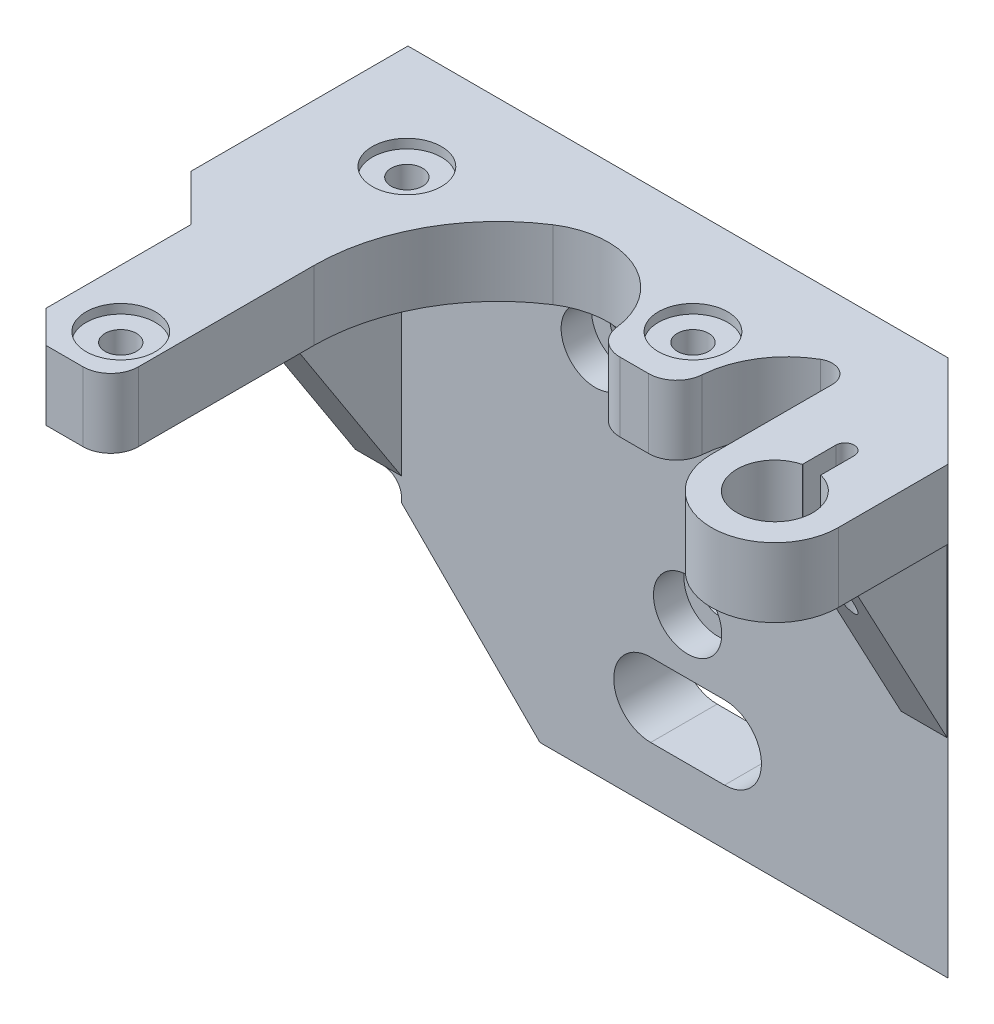
SolidWorks part; units mm, degrees
material "ABS"
ref_plane "Płaszczyzna przednia" through (0, 0, 0) normal (0, 0, 1) x (1, 0, 0)
ref_plane "Płaszczyzna górna" through (0, 0, 0) normal (0, 1, 0) x (1, 0, 0)
ref_plane "Płaszczyzna prawa" through (0, 0, 0) normal (1, 0, 0) x (0, 0, -1)
sketch "Szkic1" plane through (0, 0, 0) normal (0, 0, 1) x (1, 0, 0)
  line L0 (0, -10) -> (0, 10) construction
  line L1 (-10, 10) -> (10, 10) construction
  line L3 (-34, 22.5) -> (31, 22.5)
  line L4 (-34, 22.5) -> (-34, -30)
  line L5 (-34, -30) -> (31, -30)
  line L6 (31, 22.5) -> (31, -30)
  circle A0 centre (10, 10) radius 1.7
  circle A1 centre (-10, 10) radius 1.7
  circle A2 centre (0, -10) radius 1.7
  point P4 (0, 0)
  point P8 (0, 10)
  dimension "D1" = 3.4
  dimension "D2" = 20
  dimension "D3" = 20
  dimension "D4" = 24
  dimension "D5" = 21
  dimension "D6" = 20
  dimension "D7" = 12.5
extrude "Dodanie-wyciągnięcie1" add sketch "Szkic1" along normal blind 7.2
sketch "Szkic2" plane through (0, 0, 0) normal (0, 0, -1) x (-1, 0, 0)
  line L1 (-31, -30) -> (-8.8, -30)
  line L2 (-31, -30) -> (-31, -12.8)
  line L3 (-31, -12.8) -> (-8.8, -12.8)
  line L4 (-8.8, -30) -> (-8.8, -12.8)
  circle A0 centre (0, -10) radius 1.7 construction
  dimension "D1" = 8.8
  dimension "D2" = 2.8
extrude "Wytnij-wyciągnięcie1" cut sketch "Szkic2" against normal blind 3.4
fillet "Zaokrąglenie1" radius 2 1 edges at (8.8, -21.4, 3.4)
sketch "Szkic3" plane through (0, 0, 7.2) normal (0, 0, -1) x (-1, 0, 0)
  circle A0 centre (-10, 10) radius 3.7
  circle A1 centre (10, 10) radius 3.7
  circle A2 centre (0, -10) radius 3.7
  dimension "D1" = 7.4
extrude "Wytnij-wyciągnięcie2" cut sketch "Szkic3" along normal blind 3.3
sketch "Szkic4" plane through (0, 0, 7.2) normal (0, 0, 1) x (1, 0, 0)
  line L1 (31, 22.5) -> (20.5, 22.5)
  line L2 (31, 22.5) -> (31, 15)
  line L3 (31, 15) -> (20.5, 15)
  line L4 (20.5, 22.5) -> (20.5, 15)
  point P4 (10, 10)
  dimension "D1" = 10.5
  dimension "D2" = 5
extrude "Dodanie-wyciągnięcie2" add sketch "Szkic4" along normal blind 42
sketch "Szkic5" plane through (0, 22.5, 0) normal (0, 1, 0) x (1, 0, 0)
  line L0 (24.75, -43.865) -> (24.75, -12.865) construction
  line L1 (24.75, -12.865) -> (24.75, -7.2) construction
  line L2 (24.75, -7.2) -> (10, -7.2) construction
  line L3 (6.3, -7.2) -> (13.7, -7.2) construction
  circle A0 centre (24.75, -12.865) radius 3.75
  circle A1 centre (24.75, -43.865) radius 3.75
  dimension "D1" = 14.75
  dimension "D2" = 7.5
  dimension "D3" = 5.665
  dimension "D4" = 31
extrude "Wytnij-wyciągnięcie3" cut sketch "Szkic5" against normal blind 1
sketch "Szkic6" plane through (0, 21.5, 0) normal (0, 1, 0) x (1, 0, 0)
  circle A0 centre (24.75, -43.865) radius 1.7
  circle A1 centre (24.75, -12.865) radius 1.7
  dimension "D1" = 3.4
extrude "Wytnij-wyciągnięcie4" cut sketch "Szkic6" against normal up to next
fillet "Zaokrąglenie2" radius 20 1 edges at (20.5, 18.75, 7.2)
chamfer "Sfazowanie1" distance 3.5 angle 45 1 edges at (31, 18.75, 49.2)
sketch "Szkic7" plane through (0, 0, 7.2) normal (0, 0, 1) x (1, 0, 0)
  line L0 (0.5, 22.5) -> (-34, 22.5) construction
  line L1 (-1.75, 22.5) -> (-10.75, 22.5)
  line L2 (-1.75, 22.5) -> (-1.75, 15)
  line L3 (-1.75, 15) -> (-10.75, 15)
  line L4 (-10.75, 22.5) -> (-10.75, 15)
  line L5 (0.5, 15) -> (31, 15) construction
  line L6 (-34, 22.5) -> (-34, -30) construction
  dimension "D1" = 23.25
  dimension "D2" = 9
extrude "Dodanie-wyciągnięcie3" add sketch "Szkic7" along normal blind 12
sketch "Szkic8" plane through (0, 22.5, 0) normal (0, 1, 0) x (1, 0, 0)
  line L0 (24.75, -43.865) -> (24.75, -12.865) construction
  line L1 (24.75, -12.865) -> (-6.25, -12.865) construction
  circle A0 centre (-6.25, -12.865) radius 1.7
  circle A1 centre (24.75, -12.865) radius 1.7 construction
extrude "Wytnij-wyciągnięcie5" cut sketch "Szkic8" against normal up to next
sketch "Szkic9" plane through (0, 22.5, 0) normal (0, 1, 0) x (1, 0, 0)
  circle A0 centre (-6.25, -12.865) radius 3.75
  circle A1 centre (24.75, -12.865) radius 3.75 construction
extrude "Wytnij-wyciągnięcie6" cut sketch "Szkic9" against normal up to surface (1 mm away) up to face at (24.75, 21.5, 14.565)
fillet "Zaokrąglenie3" radius 10 2 edges at (-1.75, 18.75, 7.2) (-10.75, 18.75, 7.2)
fillet "Zaokrąglenie4" radius 8.5 1 edges at (5.0524, 18.75, 7.725)
sketch "Szkic10" plane through (31, 0, 0) normal (1, 0, 0) x (0, 0, -1)
  line L0 (0, 22.5) -> (-25, 22.5)
  line L2 (-25, 22.5) -> (-25, 15)
  line L3 (-45.7, 15) -> (-7.2, 15) construction
  line L4 (-25, 15) -> (-7.2, -12.5)
  line L5 (-7.2, -30) -> (-7.2, 15) construction
  line L6 (-7.2, -12.5) -> (0, -12.5)
  line L7 (0, -12.8) -> (0, 22.5) construction
  line L8 (0, -12.5) -> (0, 22.5)
  dimension "D1" = 35
  dimension "D2" = 25
extrude "Dodanie-wyciągnięcie4" add sketch "Szkic10" along normal blind 5
chamfer "Sfazowanie2" distance 5 angle 45 1 edges at (31, 18.75, 25)
fillet "Zaokrąglenie5" radius 3 3 edges at (-1.75, 18.75, 19.2) (-10.75, 18.75, 19.2) (20.5, 18.75, 49.2)
chamfer "Sfazowanie3" distance 15 angle 45 1 edges at (31, -30, 5.3)
chamfer "Sfazowanie4" distance 5 angle 45 1 edges at (-34, -30, 3.6)
chamfer "Sfazowanie5" distance 1.5 angle 70 1 edges at (1, 22.5, 0) first distance on face at (-6.25, 22.5, 16.615)
fillet "Zaokrąglenie6" radius 2 1 edges at (31, -12.5, 3.6)
sketch "Szkic11" plane through (0, 22.5, 0) normal (0, 1, 0) x (1, 0, 0)
  line L0 (-34, 0) -> (36, 0) construction
  line L1 (-25.625, -19.27) -> (-25.625, -15.77) construction
  line L2 (-26.625, -19.27) -> (-26.625, -15.77)
  line L3 (-24.625, -19.27) -> (-24.625, -15.77)
  line L4 (-34, -7.2) -> (-34, -1.5) construction
  line L5 (-32.5, -7.2) -> (-32.5, -23.37)
  line L6 (-20.75, -7.2) -> (-34, -7.2) construction
  line L7 (-18.75, -23.37) -> (-18.75, -7.402)
  line L8 (-20.75, -7.2) -> (-32.5, -7.2)
  circle A0 centre (-25.625, -23.37) radius 4.1
  arc A1 (-26.625, -19.27) -> (-24.625, -19.27) centre (-25.625, -19.27) ccw
  arc A2 (-24.625, -15.77) -> (-26.625, -15.77) centre (-25.625, -15.77) ccw
  arc A3 (-32.5, -23.37) -> (-18.75, -23.37) centre (-25.625, -23.37) ccw
  arc A4 (-10.7796, -16.4308) -> (-20.75, -7.2) centre (-20.75, -17.2) ccw construction
  arc A5 (-18.75, -7.402) -> (-20.75, -7.2) centre (-20.75, -17.2) ccw
  point P2 (-25.625, -17.52)
  line M13 (-34, -7.2) -> (-20.75, -7.2)
  arc M14 (-20.75, -7.2) -> (-10.7796, -16.4308) centre (-20.75, -17.2) cw
  dimension "D1" = 8.2
  dimension "D3" = 1
  dimension "D6" = 1.5
  dimension "D2" = 23.37
  dimension "D4" = 3.5
  dimension "D7" = 13.75
extrude "Dodanie-wyciągnięcie5" add sketch "Szkic11" against normal blind 7.5 contours L5 A3 L7 A2 L3 A1 A0 L2 M14 M13 region at (-26.625, 22.5, 7.4684)
ref_plane "Płaszczyzna1" through (-25.625, 0, 0) normal (-1, 0, 0) x (0, 0, 1)
sketch "Szkic12" plane through (-25.625, 0, 0) normal (-1, 0, 0) x (0, 0, 1)
  line L0 (19.2, 15) -> (7.2, -7.5)
  line L1 (7.2, 15) -> (23.37, 15) construction
  line L2 (7.2, 22.5) -> (7.2, -25) construction
  line L3 (19.2, 15) -> (7.2, 15)
  line L4 (7.2, 15) -> (7.2, -7.5)
  dimension "D1" = 22.5
  dimension "D2" = 12
extrude "Dodanie-wyciągnięcie6" add sketch "Szkic12" along normal mid plane 5
sketch "Szkic13" plane through (0, 15, 0) normal (0, 1, 0) x (1, 0, 0)
  line L3 (-26.625, -15.77) -> (-26.625, -19.2)
  line L4 (-26.625, -19.2) -> (-24.625, -19.2)
  line L5 (-24.625, -19.2) -> (-24.625, -15.77)
  line L6 (-26.625, -15.77) -> (-26.625, -19.2)
  line L7 (-26.625, -19.2) -> (-24.625, -19.2)
  line L8 (-24.625, -19.2) -> (-24.625, -15.77)
  arc A1 (-24.625, -15.77) -> (-26.625, -15.77) centre (-25.625, -15.77) ccw
  arc A2 (-24.625, -15.77) -> (-26.625, -15.77) centre (-25.625, -15.77) ccw
  dimension "D1" = 0
extrude "Wytnij-wyciągnięcie7" cut sketch "Szkic13" against normal up to next
fillet "Zaokrąglenie7" radius 2 2 edges at (-32.5, 18.75, 7.2) (-18.75, 18.75, 7.402)
sketch "Szkic14" plane through (0, 0, 0) normal (0, 0, -1) x (-1, 0, 0)
  line L0 (-4, -24) -> (4, -24) construction
  line L1 (4, -16) -> (-4, -16) construction
  line L2 (-4, -24) -> (4, -24)
  line L3 (4, -16) -> (-4, -16)
  arc A0 (4, -24) -> (4, -16) centre (4, -20) ccw construction
  arc A1 (-4, -16) -> (-4, -24) centre (-4, -20) ccw construction
  arc A2 (4, -24) -> (4, -16) centre (4, -20) ccw
  arc A3 (-4, -16) -> (-4, -24) centre (-4, -20) ccw
extrude "Wytnij-wyciągnięcie8" cut sketch "Szkic14" against normal up to next
sketch "Szkic15" plane through (0, 0, 0) normal (0, 0, -1) x (-1, 0, 0)
  line L0 (-24, -12.8) -> (-24, -5.3) construction
  line L1 (-10.8, -12.8) -> (-31.9464, -12.8) construction
  line L3 (-29, 2.2) -> (-19, 2.2)
  line L4 (-29, 2.2) -> (-29, -12.8)
  line L5 (-29, -12.8) -> (-19, -12.8)
  line L6 (-19, 2.2) -> (-19, -12.8)
  line L7 (-24, -12.8) -> (-24, 2.2) construction
  line L8 (-29, -5.3) -> (-19, -5.3) construction
  dimension "D1" = 15
  dimension "D2" = 10
  dimension "D3" = 24
extrude "Wytnij-wyciągnięcie9" cut sketch "Szkic15" against normal up to surface (3.4 mm away) up to face at (21.8876, -19.1629, 3.4)
chamfer "Sfazowanie6" distance 13 angle 45 1 edges at (-34, -3.3106, 0)
mirror "Lustro1" about plane through (-32.5, 15, 0) normal (-1, 0, 0) of bodies 116 114
delete or keep bodies "Obiekt-Usuń/zachowaj 1" type delete bodies bodies 116
